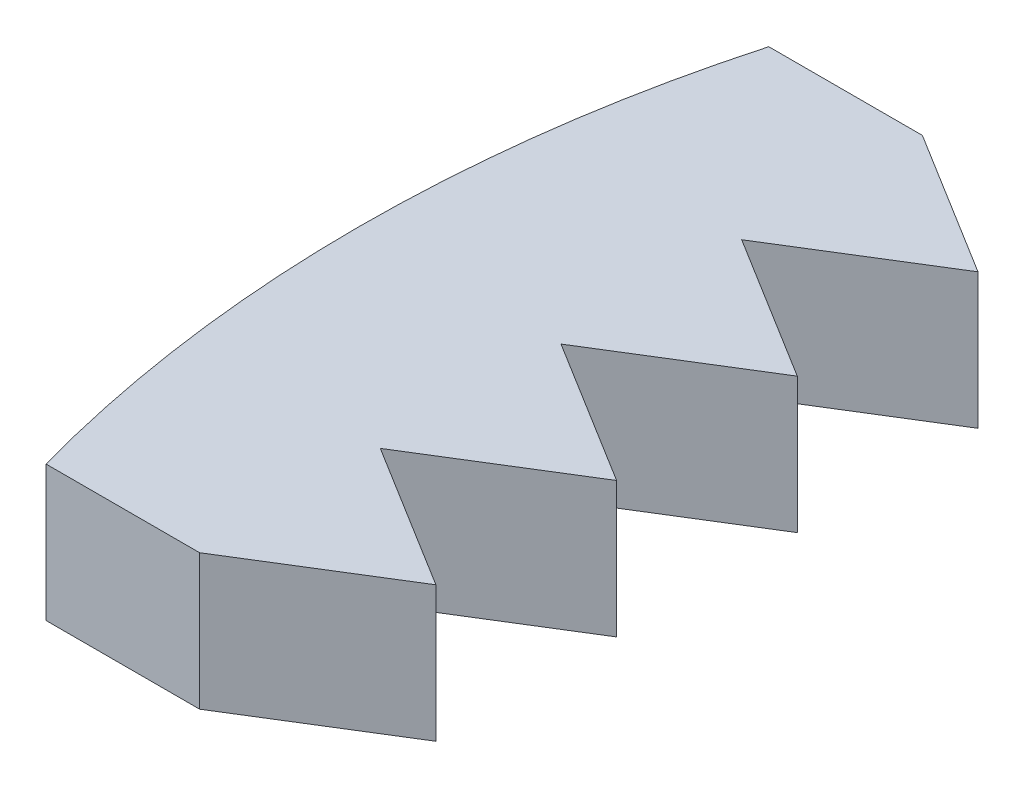
SolidWorks part; units mm, degrees
ref_plane "Front Plane" through (0, 0, 0) normal (0, 0, 1) x (1, 0, 0)
ref_plane "Top Plane" through (0, 0, 0) normal (0, 1, 0) x (1, 0, 0)
ref_plane "Right Plane" through (0, 0, 0) normal (1, 0, 0) x (0, 0, -1)
sketch "Sketch1" plane through (0, 0, 0) normal (0, 1, 0) x (1, 0, 0)
  line L0 (-30.7937, 27.5602) -> (-26.6902, 25.0202)
  line L1 (-26.6902, 25.0202) -> (-30.7937, 22.4802)
  line L2 (-30.7937, 22.4802) -> (-26.6902, 19.9402)
  line L3 (-26.6902, 19.9402) -> (-30.7937, 17.4002)
  line L4 (-30.7937, 17.4002) -> (-26.6902, 14.8602)
  line L5 (-26.6902, 14.8602) -> (-30.7937, 12.3202)
  line L6 (-30.7937, 12.3202) -> (-26.6902, 9.7802)
  line L7 (-26.6902, 9.7802) -> (-30.7937, 7.2402)
  line L8 (-30.7937, 7.2402) -> (-35.1117, 7.2402)
  line L10 (-35.1117, 27.5602) -> (-30.7937, 27.5602)
  line L11 (-30.7937, 17.4002) -> (-34.8407, 17.4002) construction
  arc A1 (-35.1117, 27.5602) -> (-35.1117, 7.2402) centre (1.6086, 17.4002) ccw
  point P13 (0, 0)
  point P14 (0, 0)
  point P17 (0, 0)
  point P18 (0, 0)
  dimension "D4" = 76.2
  dimension "D3" = 4.318
  dimension "D1" = 4.826
  dimension "D2" = 5.08
extrude "Boss-Extrude1" add sketch "Sketch1" along normal blind 3.81
